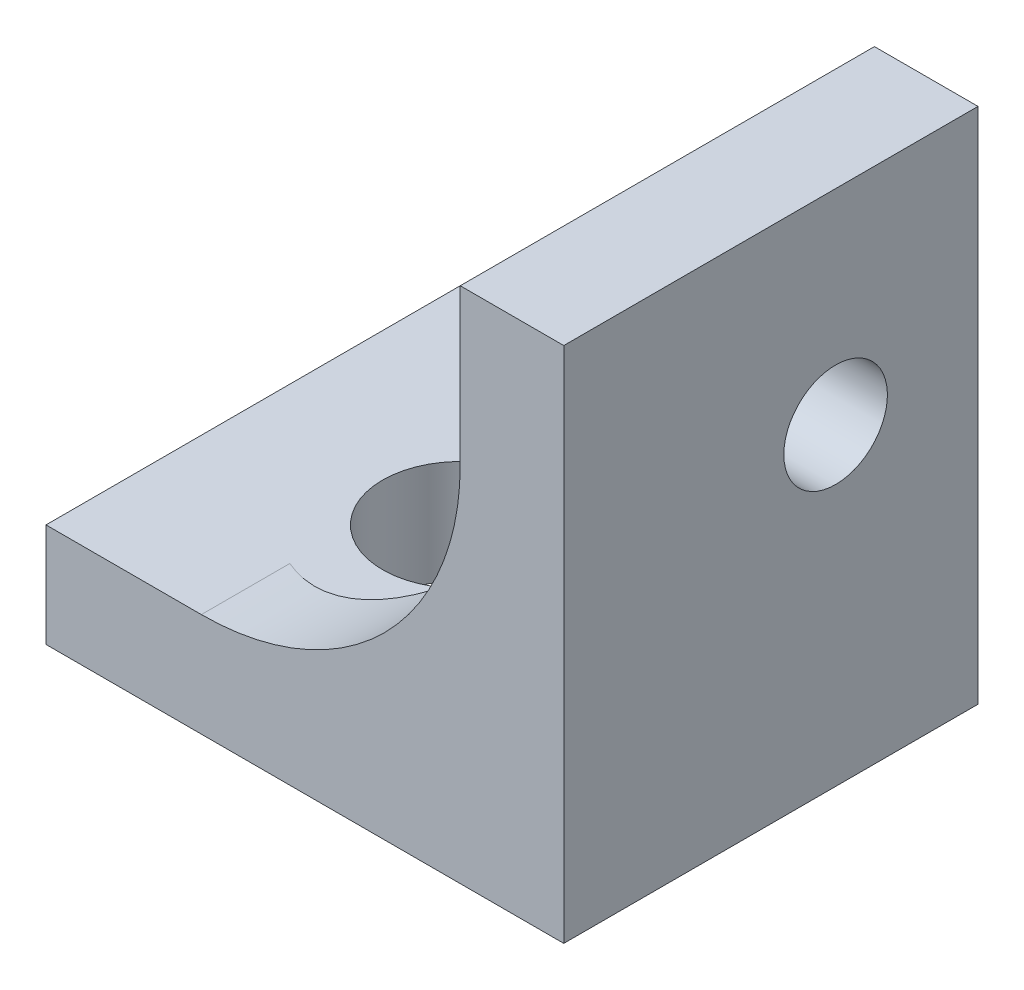
SolidWorks part; units mm, degrees
ref_plane "Front Plane" through (0, 0, 0) normal (0, 0, 1) x (1, 0, 0)
ref_plane "Top Plane" through (0, 0, 0) normal (0, 1, 0) x (1, 0, 0)
ref_plane "Right Plane" through (0, 0, 0) normal (1, 0, 0) x (0, 0, -1)
sketch "Sketch1" plane through (0, 0, 0) normal (0, 0, 1) x (1, 0, 0)
  line L0 (-10, 0) -> (0, 0)
  line L1 (0, 0) -> (0, 10)
  line L2 (0, 10) -> (-2, 10)
  line L3 (-2, 10) -> (-2, 2)
  line L4 (-2, 2) -> (-10, 2)
  line L5 (-10, 2) -> (-10, 0)
  dimension "D1" = 10
  dimension "D2" = 10
  dimension "D3" = 2
  dimension "D4" = 2
extrude "Boss-Extrude1" add sketch "Sketch1" along normal mid plane 8
sketch "Sketch2" plane through (0, 2, 0) normal (0, 1, 0) x (1, 0, 0)
  line L0 (-10, 0) -> (-2, 0) construction
  line L1 (-10, -4) -> (-10, 4) construction
  line L2 (-2, -4) -> (-2, 4) construction
  circle A0 centre (-6, 0) radius 1.5
  dimension "D1" = 3
extrude "Cut-Extrude1" cut sketch "Sketch2" against normal blind 8
sketch "Sketch3" plane through (-2, 0, 0) normal (-1, 0, 0) x (0, 0, 1)
  line L0 (-1.25, 10) -> (-1.25, 2) construction
  line L1 (4, 10) -> (-4, 10) construction
  line L2 (4, 2) -> (-4, 2) construction
  line L3 (-4, 6.05) -> (4, 6.05) construction
  line L4 (-4, 10) -> (-4, 2) construction
  line L5 (4, 10) -> (4, 2) construction
  line L6 (4, 0) -> (-4, 0) construction
  circle A0 centre (-1.25, 6.05) radius 1
  point P16 (5.25, 6.05)
  point P17 (-1.25, 6.05)
  dimension "D3" = 2
  dimension "D1" = 2.75
  dimension "D2" = 6.05
extrude "Cut-Extrude2" cut sketch "Sketch3" against normal blind 8
fillet "Fillet1" radius 5 1 edges at (-2, 2, 0)
sketch "Sketch4" plane through (0, 2, 0) normal (0, 1, 0) x (1, 0, 0)
  circle A0 centre (-6, 0) radius 2.5
  arc A2 (-7, -1.118) -> (-7, 1.118) centre (-6, 0) ccw construction
  dimension "D1" = 5
extrude "Cut-Extrude3" cut sketch "Sketch4" along normal blind 8
sketch "Sketch5" plane through (-2, 0, 0) normal (-1, 0, 0) x (0, 0, 1)
  circle A0 centre (-1.25, 6.05) radius 1.75
  arc A1 (-1.5622, 7) -> (-0.9378, 7) centre (-1.25, 6.05) ccw construction
  dimension "D1" = 3.5
extrude "Cut-Extrude4" cut sketch "Sketch5" along normal blind 8
